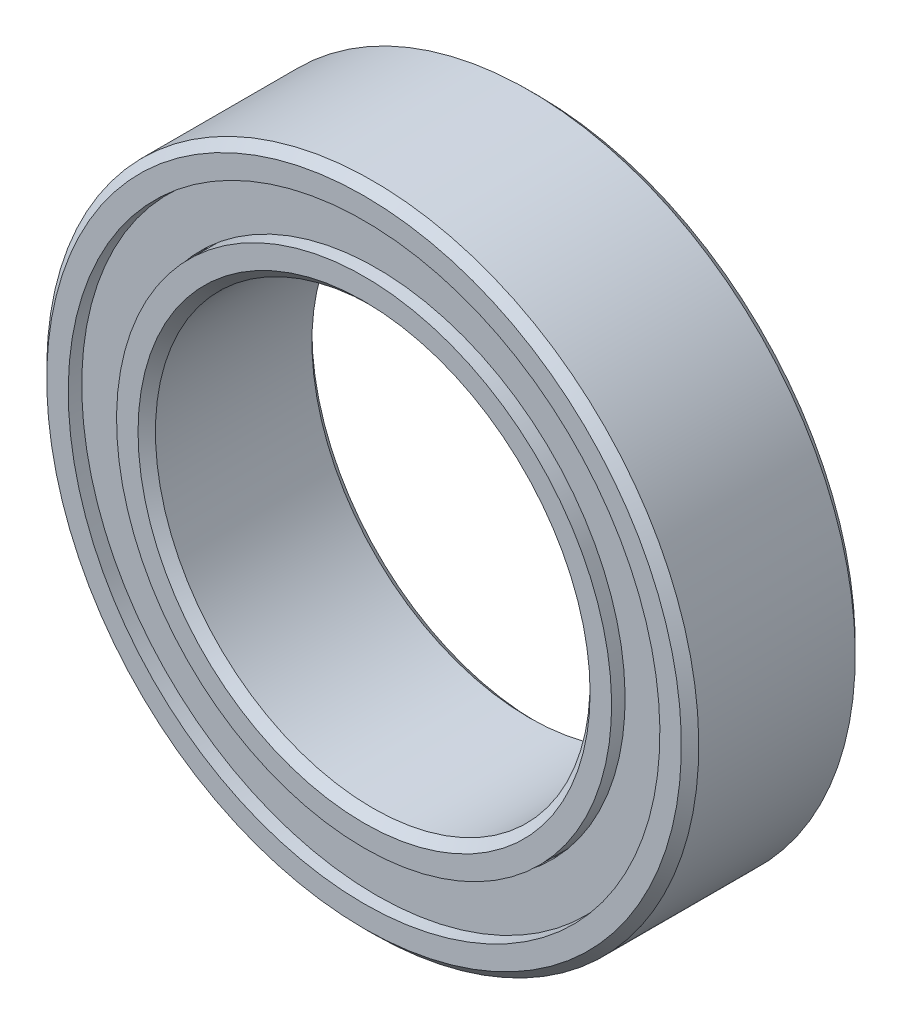
SolidWorks part; units mm, degrees
ref_plane "Front Plane" through (0, 0, 0) normal (0, 0, 1) x (1, 0, 0)
ref_plane "Top Plane" through (0, 0, 0) normal (0, 1, 0) x (1, 0, 0)
ref_plane "Right Plane" through (0, 0, 0) normal (1, 0, 0) x (0, 0, -1)
sketch "Sketch1" plane through (0, 0, 0) normal (0, 0, 1) x (1, 0, 0)
  circle A0 centre (0, 0) radius 7.5
  circle A1 centre (0, 0) radius 5
  dimension "OD" = 15
  dimension "ID" = 10
  dimension "For Shaft Diameter" = 10
  dimension "For Housing ID" = 15
sketch "Sketch8" plane through (0, 0, 0) normal (1, 0, 0) x (0, 0, -1)
  line L1 (-2, 7.5) -> (2, 7.5)
  line L2 (-2, 7.5) -> (-2, -7.5)
  line L3 (-2, -7.5) -> (2, -7.5)
  line L4 (2, 7.5) -> (2, -7.5)
  line L5 (-2, 7.5) -> (2, -7.5) construction
  line L6 (-2, -7.5) -> (2, 7.5) construction
  point P0 (0, 0)
  point P6 (0, -7.5)
  dimension "Width" = 4
sketch "Sketch5" plane through (0, 0, 0) normal (1, 0, 0) x (0, 0, -1)
  line L0 (-2, 0) -> (2, 0) construction
  line L1 (0, 7.5) -> (0, -7.5) construction
  line L2 (1.8, 7.5) -> (-1.8, 7.5)
  line L3 (-1.8, 7.5) -> (-2, 7.3)
  line L4 (-2, 7.3) -> (-2, 6.8056)
  line L5 (-2, 6.8056) -> (-0.8889, 6.8056)
  line L6 (2, 6.8056) -> (0.8889, 6.8056)
  line L7 (2, 7.3) -> (2, 6.8056)
  line L8 (1.8, 7.5) -> (2, 7.3)
  line L9 (0, 7.5) -> (0, 6.25) construction
  line L10 (0, 6.25) -> (0, 5) construction
  line L11 (-1.0482, 6.25) -> (-2, 6.25) construction
  line L12 (1.3336, 5.7198) -> (1.7146, 5.7198)
  line L13 (-1.3336, 5.7198) -> (-1.7146, 5.7198)
  line L14 (-1.3336, 5.7198) -> (-1.3336, 6.7802)
  line L15 (-1.3336, 6.7802) -> (-1.7146, 6.7802)
  line L16 (-1.7146, 5.7198) -> (-1.7146, 6.7802)
  line L17 (-1.3336, 5.7198) -> (-1.7146, 6.7802) construction
  line L18 (-1.3336, 6.7802) -> (-1.7146, 5.7198) construction
  line L19 (1.7146, 5.7198) -> (1.7146, 6.7802)
  line L20 (1.3336, 6.7802) -> (1.7146, 6.7802)
  line L21 (1.3336, 5.7198) -> (1.3336, 6.7802)
  line L22 (0, 7.5) -> (0, -7.5) construction
  line L23 (2, 0) -> (2, 7.5) construction
  line L24 (2, 7.5) -> (1.8, 7.5) construction
  line L25 (-2, 0) -> (-2, 7.5) construction
  line L26 (-2, 7.5) -> (-1.8, 7.5) construction
  line L27 (2, 0) -> (2, -7.5) construction
  line L28 (-2, 0) -> (-2, -7.5) construction
  line L29 (-2, -7.5) -> (2, -7.5) construction
  arc A0 (-0.8889, 6.8056) -> (0.8889, 6.8056) centre (0, 6.25) cw
  circle A1 centre (0, 6.25) radius 1.0482 construction
  point P14 (0, 5)
  point P15 (-1.5241, 6.25)
  dimension "D1" = 45
  dimension "D2" = 0.2
  dimension "D3" = 1.7778
  dimension "D4" = 0.5556
  dimension "D5" = 0.381
  dimension "D6" = 0.0254
revolve "Revolve1" add sketch "Sketch5" angle 360 about L0
sketch "Sketch3" plane through (0, 0, 0) normal (1, 0, 0) x (0, 0, -1)
  line L0 (-2, 5.6944) -> (-0.8889, 5.6944)
  line L1 (0, 7.5) -> (0, -7.5) construction
  line L2 (-2, 7.3) -> (-2, 6.8056) construction
  line L3 (-2, 5.6944) -> (-2, 5.2)
  line L4 (-1.8, 7.5) -> (-2, 7.3) construction
  line L5 (-2, 5.2) -> (-1.8, 5)
  line L6 (-1.8, 5) -> (1.8, 5)
  line L7 (1.8, 7.5) -> (1.8, -7.5) construction
  line L8 (1.8, 5) -> (2, 5.2)
  line L9 (2, -7.3) -> (2, 7.3) construction
  line L10 (2, 5.2) -> (2, 5.6944)
  line L11 (2, 5.6944) -> (0.8889, 5.6944)
  line L13 (1.8, 7.5) -> (2, 7.3) construction
  arc A0 (0.8889, 6.8056) -> (-0.8889, 6.8056) centre (0, 6.25) ccw construction
  arc A1 (0.8889, 5.6944) -> (-0.8889, 5.6944) centre (0, 6.25) cw
revolve "Revolve3" add sketch "Sketch3" angle 360 about L0
sketch "Sketch4" plane through (0, 0, 0) normal (1, 0, 0) x (0, 0, -1)
  line L0 (-1.0482, 6.25) -> (1.0482, 6.25)
  arc A2 (-1.0482, 6.25) -> (1.0482, 6.25) centre (0, 6.25) cw
  arc A3 (0.8889, 6.8056) -> (-0.8889, 6.8056) centre (0, 6.25) ccw construction
revolve "Revolve4" add sketch "Sketch4" angle 360 about L0
pattern_circular "CirPattern1" count 11 every 32.727 of bodies 104
equation "\"D2@Sketch5\" = \"Width@Sketch8\" * .05"
equation "\"D3@Sketch5\" = \"Width@Sketch8\" / 2.25"
equation "\"D4@Sketch5\"=((\"OD@Sketch1\"-\"ID@Sketch1\")/2)/4.5"
equation "\"D2@CirPattern1\" = 360/\"Balls@CirPattern1\""
